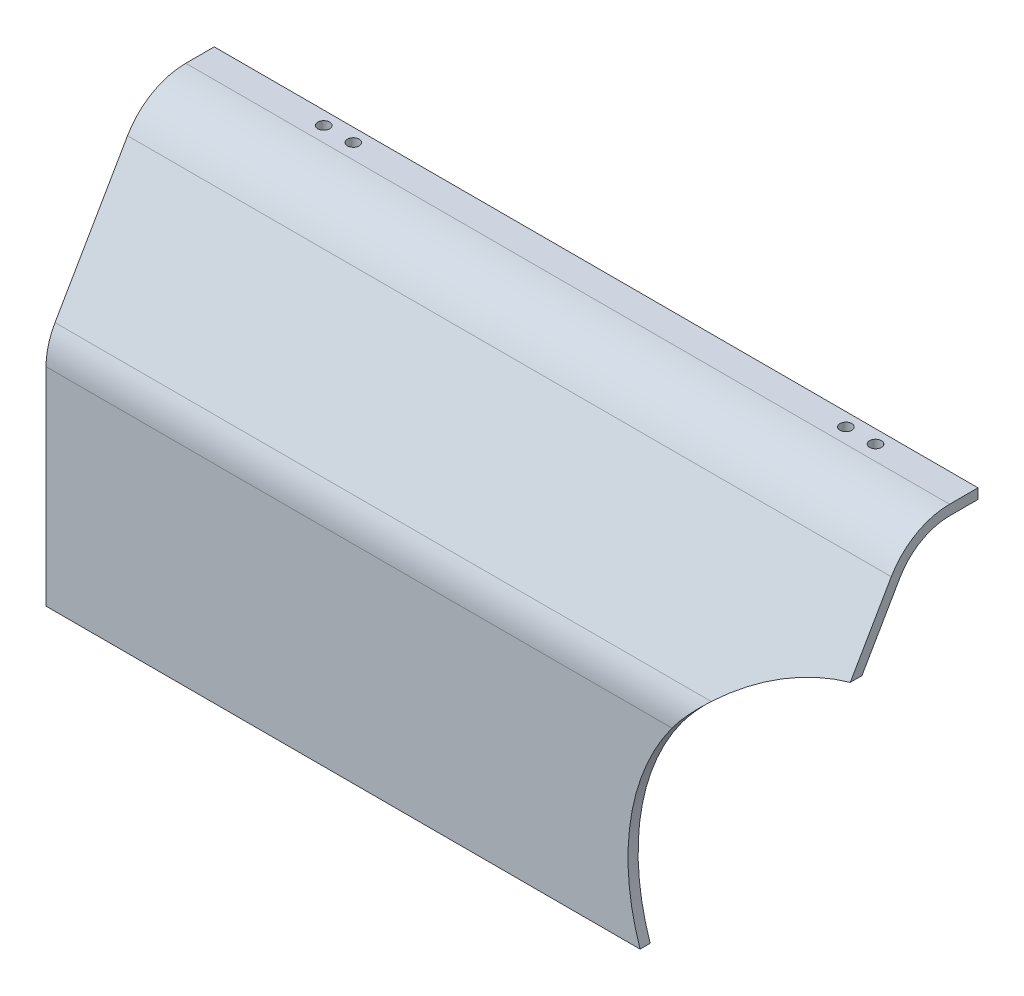
SolidWorks part; units mm, degrees
ref_plane "Alzado" through (0, 0, 0) normal (0, 0, 1) x (1, 0, 0)
ref_plane "Planta" through (0, 0, 0) normal (0, 1, 0) x (1, 0, 0)
ref_plane "Vista lateral" through (0, 0, 0) normal (1, 0, 0) x (0, 0, -1)
sketch "Croquis1" plane through (0, 0, 0) normal (1, 0, 0) x (0, 0, -1)
  line L0 (0, 0) -> (0, 66.1962)
  line L1 (0, 66.1962) -> (28.7321, 115.9615)
  line L2 (28.7321, 115.9615) -> (47, 115.9615)
  line L3 (47, 115.9615) -> (47, 118.9615)
  line L4 (47, 118.9615) -> (27, 118.9615)
  line L5 (27, 118.9615) -> (-3, 67)
  line L6 (-3, 67) -> (-3, 0)
  line L7 (-3, 0) -> (0, 0)
  line L8 (0, 66.1962) -> (29.2398, 66.1962) construction
  dimension "D1" = 3
  dimension "D2" = 3
  dimension "D3" = 3
  dimension "D4" = 67
  dimension "D5" = 60
  dimension "D6" = 20
  dimension "D7" = 60
extrude "Saliente-Extruir1" add sketch "Croquis1" along normal mid plane 227
fillet "Redondeo1" radius 20 1 edges at (0, 67, 3)
fillet "Redondeo2" radius 20 1 edges at (0, 118.9615, -27)
fillet "Redondeo3" radius 17 1 edges at (0, 115.9615, -28.7321)
fillet "Redondeo4" radius 17 1 edges at (0, 66.1962, 0)
sketch "Croquis2" plane through (0, 0, 3) normal (0, 0, 1) x (1, 0, 0)
  circle A0 centre (126.88, 22.7215) radius 70
  dimension "D1" = 140
  dimension "D2" = 13.38
  dimension "D3" = 86.24
extrude "Cortar-Extruir1" [suppressed] cut sketch "Croquis2" against normal through all
sketch "Croquis4" plane through (0, 118.9615, 0) normal (0, 1, 0) x (1, 0, 0)
  circle A0 centre (-77, 43.047) radius 1.75
  circle A1 centre (-68.2, 43.047) radius 1.75
extrude "Cortar-Extruir3" cut sketch "Croquis4" against normal blind 4
sketch "Croquis5" plane through (0, 118.9615, 0) normal (0, 1, 0) x (1, 0, 0)
  circle A0 centre (78.2, 43.047) radius 1.75
  circle A1 centre (87, 43.047) radius 1.75
  dimension "D1" = 3.5
extrude "Cortar-Extruir4" cut sketch "Croquis5" against normal blind 4
sketch "Croquis7" plane through (0, 0, 3) normal (0, 0, 1) x (1, 0, 0)
  circle A0 centre (126.9781, 21.7215) radius 67.5
  dimension "D1" = 135
extrude "Cortar-Extruir6" cut sketch "Croquis7" against normal through all
